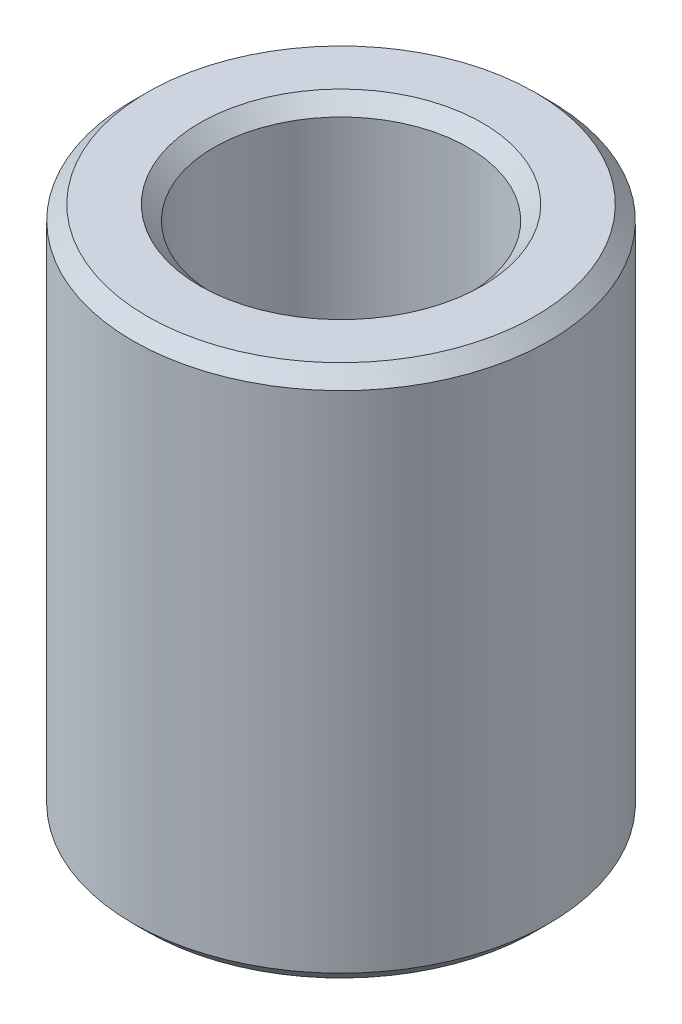
SolidWorks part; units mm, degrees
ref_plane "Front Plane" through (0, 0, 0) normal (0, 0, 1) x (1, 0, 0)
ref_plane "Top Plane" through (0, 0, 0) normal (0, 1, 0) x (1, 0, 0)
ref_plane "Right Plane" through (0, 0, 0) normal (1, 0, 0) x (0, 0, -1)
sketch "Sketch1" plane through (0, 0, 0) normal (0, 1, 0) x (1, 0, 0)
  circle A0 centre (0, 0) radius 50
  dimension "SLEEVE_OD" = 100
extrude "Boss-Extrude1" add sketch "Sketch1" along normal blind 128.0158
sketch "Sketch2" plane through (0, 0, 0) normal (0, 1, 0) x (1, 0, 0)
  circle A0 centre (0, 0) radius 30.5191
  dimension "BORE_D" = 61.0382
extrude "Cut-Extrude1" cut sketch "Sketch2" along normal through all
chamfer "Chamfer1" distance 3.4068 angle 45 4 edges at (0, 128.0158, 30.5191) (0, 0, 30.5191) (0, 0, 50) (0, 128.0158, 50)
